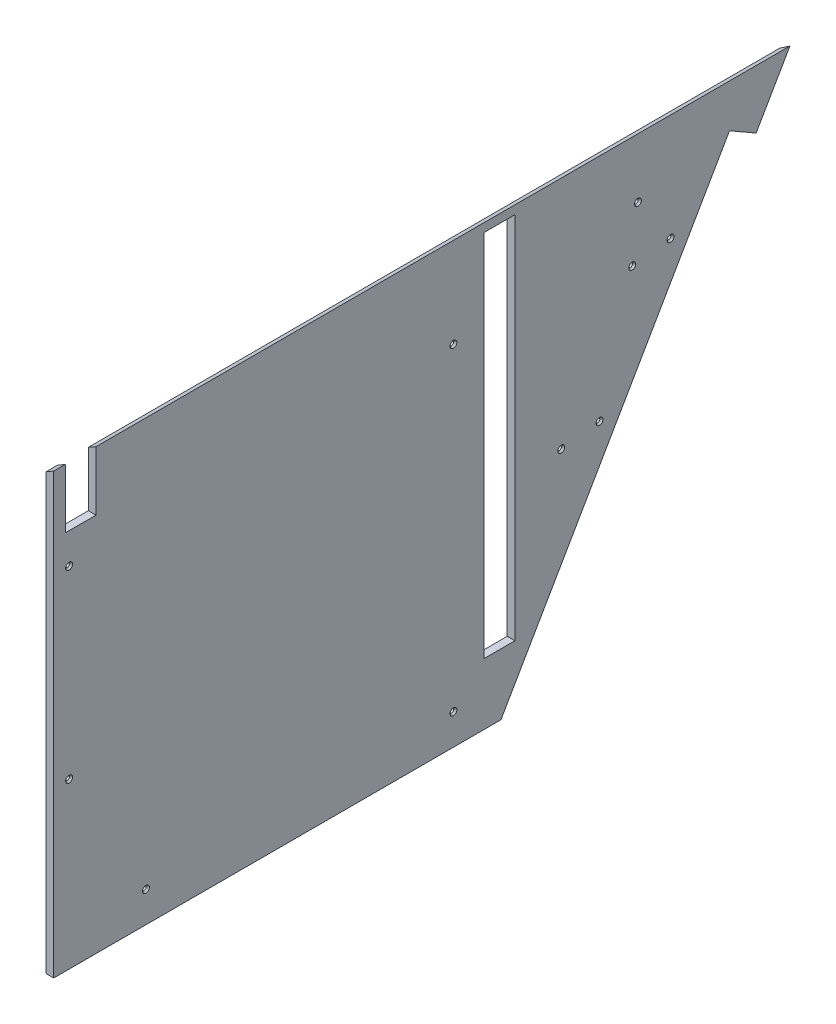
SolidWorks part; units mm, degrees
material "Acrylic (Medium-high impact)"
ref_plane "Front Plane" through (0, 0, 0) normal (0, 0, 1) x (1, 0, 0)
ref_plane "Top Plane" through (0, 0, 0) normal (0, 1, 0) x (1, 0, 0)
ref_plane "Right Plane" through (0, 0, 0) normal (1, 0, 0) x (0, 0, -1)
sketch "Sketch1" plane through (0, 0, 0) normal (1, 0, 0) x (0, 0, -1)
  line L0 (487.0358, 330.1769) -> (276.2307, -34.9481)
  line L1 (-122.5642, 330.1769) -> (487.0358, 330.1769)
  line L2 (-122.5642, 330.1769) -> (-122.5642, -34.9481)
  line L3 (-122.5642, -34.9481) -> (276.2307, -34.9481)
  dimension "D1" = 365.125
  dimension "D2" = 609.6
  dimension "D3" = 120
extrude "Boss-Extrude1" add sketch "Sketch1" along normal blind 6.35
sketch "Sketch2" plane through (6.35, 0, 0) normal (1, 0, 0) x (0, 0, -1)
  line L0 (-122.5642, 330.1769) -> (-122.5642, -34.9481) construction
  line L1 (233.0358, 320.6519) -> (258.4358, 320.6519)
  line L2 (233.0358, 320.6519) -> (233.0358, 15.8519)
  line L3 (233.0358, 15.8519) -> (258.4358, 15.8519)
  line L4 (258.4358, 320.6519) -> (258.4358, 15.8519)
  line L5 (-122.5642, -34.9481) -> (276.2307, -34.9481) construction
  dimension "D1" = 304.8
  dimension "D2" = 25.4
  dimension "D3" = 355.6
  dimension "D4" = 50.8
extrude "Cut-Extrude1" cut sketch "Sketch2" against normal through all
sketch "Sketch3" plane through (6.35, 0, 0) normal (1, 0, 0) x (0, 0, -1)
  line L0 (457.7064, 279.3769) -> (276.2307, -34.9481)
  line L1 (276.2307, -34.9481) -> (487.0358, 330.1769) construction
  line L2 (-122.5642, -34.9481) -> (276.2307, -34.9481) construction
  line L3 (246.9014, -34.9481) -> (435.7093, 292.0769)
  line L4 (435.7093, 292.0769) -> (457.7064, 279.3769)
  line L5 (487.0358, 330.1769) -> (-122.5642, 330.1769) construction
  line L6 (246.9014, -34.9481) -> (276.2307, -34.9481)
  dimension "D1" = 25.4
  dimension "D2" = 25.4
  dimension "D3" = 38.1
extrude "Cut-Extrude2" cut sketch "Sketch3" against normal through all
hole_wizard "CSK for #4 Flat Head Machine Screw3" positions "3DSketch1" profile "Sketch4" countersink size "#4" standard "ANSI Inch" end condition through all
sketch3d "3DSketch1"
  line L1 (6.35, 330.1769, 122.5642) -> (6.35, -34.9481, 122.5642) construction
  line L2 (6.35, -34.9481, 122.5642) -> (6.35, -34.9481, -246.9014) construction
  point P0 (6.35, 253.3419, 109.8642)
  point P2 (6.35, 253.3419, -207.6358)
  point P4 (6.35, 278.7419, -360.0358)
  dimension "D1" = 288.29
  dimension "D2" = 317.5
  dimension "D3" = 482.6
  dimension "D4" = 12.7
  dimension "D5" = 288.29
  dimension "D6" = 313.69
sketch "Sketch4" plane through (6.35, 253.3419, 109.8642) normal (0, 1, 0) x (0, 0, -1)
  line L0 (0, 0) -> (0, 6.35)
  line L1 (0, 6.35) -> (1.6319, 6.35)
  line L2 (1.6319, 6.35) -> (1.6319, 1.4098)
  line L3 (1.6319, 1.4098) -> (2.8575, 0)
  line L5 (2.8575, 0) -> (0, 0)
  line L6 (-1.6319, 1.4098) -> (-2.8575, 0) construction
  line L11 (0, -6.35) -> (0, 107.95) construction
  dimension "Thru Hole Dia." = 3.2639
  dimension "Thru Hole Depth" = 6.35
  dimension "Near C'Sink Dia." = 5.715
  dimension "Near C'Sink Angle" = 82
hole_wizard "CSK for #4 Flat Head Machine Screw2" positions "3DSketch3" profile "Sketch6" countersink size "#4" standard "ANSI Inch" end condition through all
sketch3d "3DSketch3"
  line L0 (6.35, 330.1769, 122.5642) -> (6.35, -34.9481, 122.5642) construction
  line L2 (6.35, -34.9481, 122.5642) -> (6.35, -34.9481, -246.9014) construction
  point P0 (6.35, 100.9419, 109.8642)
  dimension "D1" = 135.89
  dimension "D3" = 12.7
sketch "Sketch6" plane through (6.35, 100.9419, 109.8642) normal (0, 1, 0) x (0, 0, -1)
  line L0 (0, 0) -> (0, 6.35)
  line L1 (0, 6.35) -> (1.6319, 6.35)
  line L2 (1.6319, 6.35) -> (1.6319, 1.4098)
  line L3 (1.6319, 1.4098) -> (2.8575, 0)
  line L5 (2.8575, 0) -> (0, 0)
  line L6 (-1.6319, 1.4098) -> (-2.8575, 0) construction
  line L11 (0, -6.35) -> (0, 107.95) construction
  dimension "Thru Hole Dia." = 3.2639
  dimension "Thru Hole Depth" = 6.35
  dimension "Near C'Sink Dia." = 5.715
  dimension "Near C'Sink Angle" = 82
hole_wizard "CSK for #4 Flat Head Machine Screw1" positions "3DSketch4" profile "Sketch8" countersink size "#4" standard "ANSI Inch" end condition through all
sketch3d "3DSketch4"
  line L0 (6.35, -34.9481, 122.5642) -> (6.35, -34.9481, -246.9014) construction
  line L1 (6.35, 330.1769, 122.5642) -> (6.35, -34.9481, 122.5642) construction
  point P0 (6.35, -9.5481, 46.3642)
  point P2 (6.35, -9.5481, -207.6358)
  dimension "D1" = 25.4
  dimension "D2" = 25.4
  dimension "D3" = 330.2
  dimension "D4" = 76.2
sketch "Sketch8" plane through (6.35, -9.5481, 46.3642) normal (0, 1, 0) x (0, 0, -1)
  line L0 (0, 0) -> (0, 6.35)
  line L1 (0, 6.35) -> (1.6319, 6.35)
  line L2 (1.6319, 6.35) -> (1.6319, 1.4098)
  line L3 (1.6319, 1.4098) -> (2.8575, 0)
  line L5 (2.8575, 0) -> (0, 0)
  line L6 (-1.6319, 1.4098) -> (-2.8575, 0) construction
  line L11 (0, -6.35) -> (0, 107.95) construction
  dimension "Thru Hole Dia." = 3.2639
  dimension "Thru Hole Depth" = 6.35
  dimension "Near C'Sink Dia." = 5.715
  dimension "Near C'Sink Angle" = 82
hole_wizard "CSK for #4 Flat Head Machine Screw4" positions "3DSketch5" profile "Sketch9" countersink size "#4" standard "ANSI Inch" end condition through all
sketch3d "3DSketch5"
  line L0 (6.35, 292.0769, -435.7093) -> (6.35, -34.9481, -246.9014) construction
  line L2 (6.35, -34.9481, 122.5642) -> (6.35, -34.9481, -246.9014) construction
  point P0 (6.35, 235.418, -355.3371)
  point P2 (6.35, 239.4349, -386.9856)
  point P12 (6.35, 133.818, -296.6783)
  point P14 (6.35, 137.8349, -328.3268)
  dimension "D1" = 41.275
  dimension "D2" = 270.3662
  dimension "D3" = 15.875
  dimension "D4" = 31.9024
  dimension "D5" = 41.275
  dimension "D6" = 15.875
  dimension "D7" = 31.9024
  dimension "D8" = 168.7662
sketch "Sketch9" plane through (6.35, 235.418, -355.3371) normal (0, 1, 0) x (0, 0, -1)
  line L0 (0, 0) -> (0, 6.35)
  line L1 (0, 6.35) -> (1.6319, 6.35)
  line L2 (1.6319, 6.35) -> (1.6319, 1.4098)
  line L3 (1.6319, 1.4098) -> (2.8575, 0)
  line L5 (2.8575, 0) -> (0, 0)
  line L6 (-1.6319, 1.4098) -> (-2.8575, 0) construction
  line L11 (0, -6.35) -> (0, 107.95) construction
  dimension "Thru Hole Dia." = 3.2639
  dimension "Thru Hole Depth" = 6.35
  dimension "Near C'Sink Dia." = 5.715
  dimension "Near C'Sink Angle" = 82
chamfer "Chamfer1" distance 6.096 angle 60 1 edges at (0, 330.1769, -182.2358) first distance on face at (0, 235.418, -356.969)
sketch "Sketch7" plane through (6.35, 0, 0) normal (1, 0, 0) x (0, 0, -1)
  line L0 (-122.5642, 327.747) -> (-122.5642, -34.9481) construction
  line L1 (-113.0392, 327.747) -> (-87.6392, 327.747)
  line L2 (-113.0392, 327.747) -> (-113.0392, 278.7419)
  line L3 (-113.0392, 278.7419) -> (-87.6392, 278.7419)
  line L4 (-87.6392, 327.747) -> (-87.6392, 278.7419)
  line L5 (485.6329, 327.747) -> (-122.5642, 327.747) construction
  line L6 (-122.5642, -34.9481) -> (246.9014, -34.9481) construction
  dimension "D1" = 34.925
  dimension "D2" = 25.4
  dimension "D3" = 313.69
  dimension "D4" = 0
extrude "Cut-Extrude3" cut sketch "Sketch7" against normal up to next
